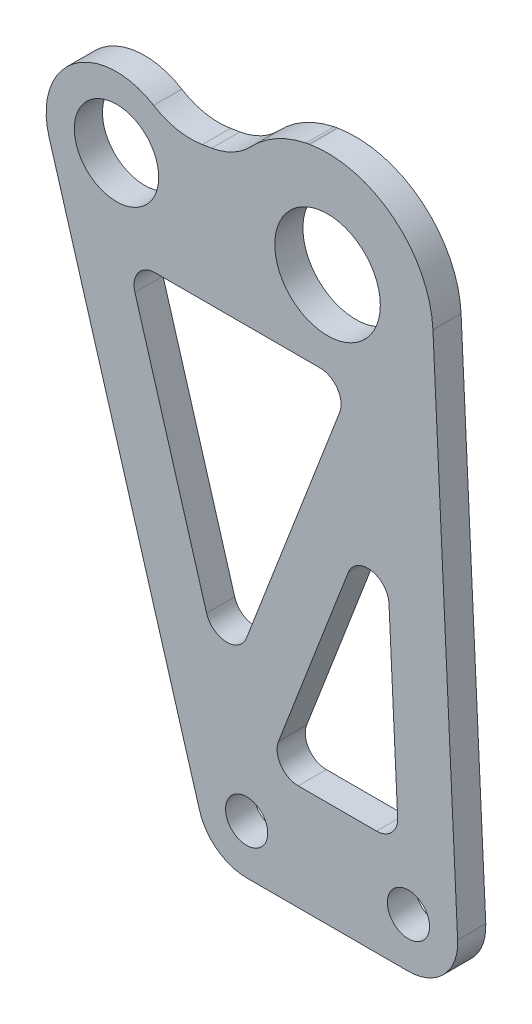
SolidWorks part; units mm, degrees
material "Thornel Mat VMA"
ref_plane "前视基准面" through (0, 0, 0) normal (0, 0, 1) x (1, 0, 0)
ref_plane "上视基准面" through (0, 0, 0) normal (0, 1, 0) x (1, 0, 0)
ref_plane "右视基准面" through (0, 0, 0) normal (1, 0, 0) x (0, 0, -1)
sketch "草图1" plane through (0, 0, 0) normal (0, 0, 1) x (1, 0, 0)
  line L0 (-11.5, 0) -> (11.5, 0) construction
  line L1 (0, 0) -> (0, 73) construction
  line L2 (0, 73) -> (-30, 73) construction
  line L3 (-39.588, 70.1592) -> (-18.2116, -1.9886)
  line L4 (-31.6667, 82.8601) -> (-2.5, 87.7902)
  line L5 (14.9829, 73.7165) -> (18.492, 0.3344)
  line L6 (-11.5, -7) -> (11.5, -7)
  circle A0 centre (11.5, 0) radius 3
  circle A1 centre (-11.5, 0) radius 3
  circle A2 centre (0, 73) radius 7.5
  circle A3 centre (-30, 73) radius 6
  arc A4 (14.9829, 73.7165) -> (-2.5, 87.7902) centre (0, 73) ccw
  arc A5 (-31.6667, 82.8601) -> (-39.588, 70.1592) centre (-30, 73) ccw
  arc A6 (11.5, -7) -> (18.492, 0.3344) centre (11.5, 0) ccw
  arc A7 (-18.2116, -1.9886) -> (-11.5, -7) centre (-11.5, 0) ccw
  point P4 (0, 0)
  dimension "D4" = 6
  dimension "D5" = 6
  dimension "D6" = 15
  dimension "D7" = 12
  dimension "D8" = 30
  dimension "D9" = 20
  dimension "D10" = 14
  dimension "D11" = 14
  dimension "D1" = 23
  dimension "D2" = 73
  dimension "D3" = 30
extrude "凸台-拉伸1" add sketch "草图1" along normal blind 4
sketch "草图3" plane through (0, 0, 4) normal (0, 0, 1) x (1, 0, 0)
  line L0 (-22.2942, 79.3734) -> (-12.6957, 80.9959)
  line L1 (-2.5, 87.7902) -> (-31.6667, 82.8601) construction
  line L2 (-31.6667, 82.8601) -> (-2.8328, 87.7339)
  arc A0 (-22.2942, 79.3734) -> (-31.6667, 82.8601) centre (-30, 73) ccw
  arc A1 (-2.8328, 87.7339) -> (-12.6957, 80.9959) centre (0, 73) ccw
  dimension "D2" = 30.0076
  dimension "D3" = 5
extrude "切除-拉伸2" cut sketch "草图3" against normal blind 10
sketch "草图7" plane through (0, 0, 4) normal (0, 0, 1) x (1, 0, 0)
  line L0 (-28.5305, 61) -> (7.5818, 61)
  line L1 (7.5818, 61) -> (10.1163, 8)
  line L2 (10.1163, 8) -> (-12.8273, 8)
  line L3 (-12.8273, 8) -> (-28.5305, 61)
  line L4 (-39.588, 70.1592) -> (-18.2116, -1.9886) construction
  line L5 (18.492, 0.3344) -> (14.9829, 73.7165) construction
  line L6 (-30, 73) -> (0, 73) construction
  line L7 (-11.5, 0) -> (11.5, 0) construction
  line L8 (7.5818, 61) -> (-12.8273, 8) construction
  line L9 (3.849, 62.4374) -> (-16.5601, 9.4374)
  line L10 (11.3146, 59.5626) -> (-9.0945, 6.5626)
  dimension "D1" = 8
  dimension "D2" = 8
  dimension "D3" = 8
  dimension "D4" = 12
  dimension "D5" = 4
  dimension "D6" = 4
extrude "切除-拉伸6" cut sketch "草图7" against normal blind 10 contours L9 L0 L3 | L1 L10 L2 region at (-13.3087, 45.4303, 4) region at (3.2102, 22.3662, 4)
fillet "圆角8" radius 3 6 edges at (10.1163, 8, 2) (8.0553, 51.0985, 2) (-14.6912, 14.2908, 2) (-28.5305, 61, 2) (3.2955, 61, 2) (-8.541, 8, 2)
fillet "圆角9" radius 10 3 edges at (-2.8328, 87.7339, 2) (-12.6957, 80.9959, 2) (-22.2942, 79.3734, 2)
